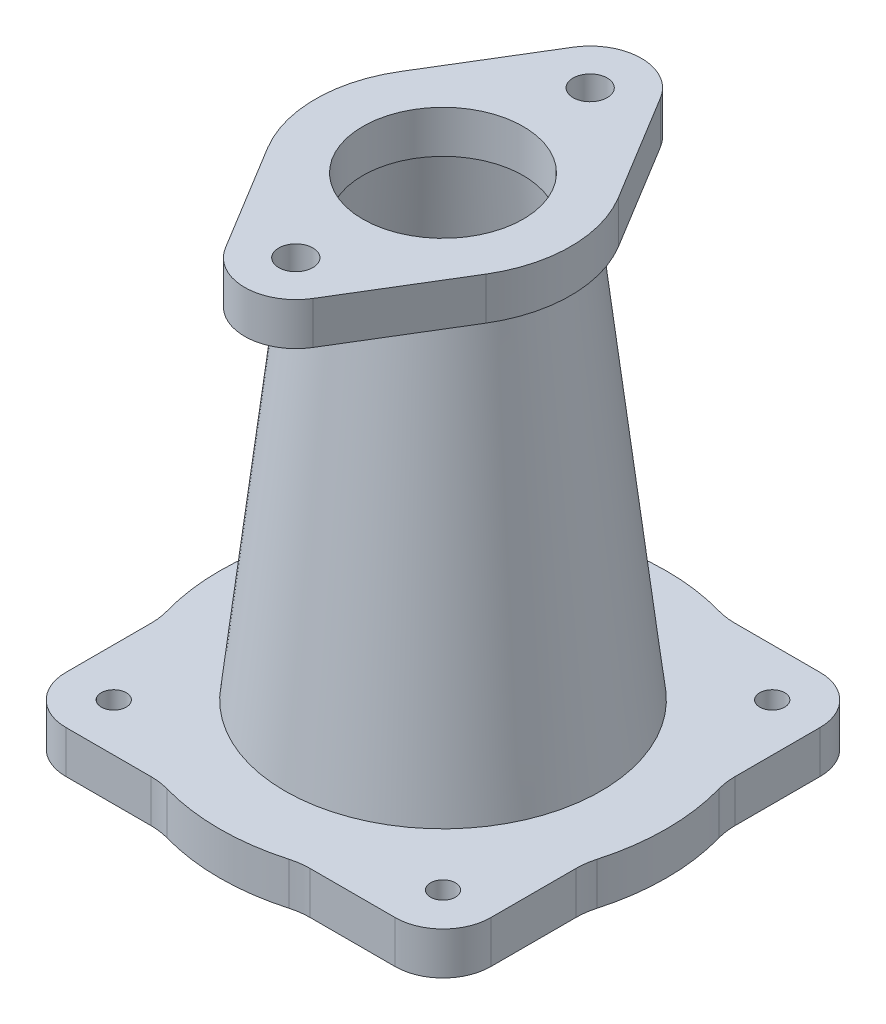
SolidWorks part; units mm, degrees
ref_plane "Front Plane" through (0, 0, 0) normal (0, 0, 1) x (1, 0, 0)
ref_plane "Top Plane" through (0, 0, 0) normal (0, 1, 0) x (1, 0, 0)
ref_plane "Right Plane" through (0, 0, 0) normal (1, 0, 0) x (0, 0, -1)
sketch "Sketch1" plane through (0, 0, 0) normal (1, 0, 0) x (0, 0, -1)
  line L0 (0, 0) -> (0, 51.6773) construction
  line L1 (12, 74.5842) -> (15.8346, 74.5842)
  line L2 (15.8346, 74.5842) -> (24.3324, 0)
  line L3 (24.3324, 0) -> (20.4978, 0)
  line L4 (20.4978, 0) -> (12, 74.5842)
  line L5 (6.7611, 0) -> (-6.7611, 0) construction
  dimension "D1" = 3.81
  dimension "D2" = 83.5
  dimension "D3" = 20.4978
  dimension "D4" = 12
revolve "Revolve1" add sketch "Sketch1" angle 360 about L0
sketch "Sketch2" plane through (0, 0, 0) normal (0, -1, 0) x (1, 0, 0)
  line L1 (0, 0) -> (0, 15.1186) construction
  line L2 (0, 0) -> (14.8797, 0) construction
  line L3 (-31.75, 11.8791) -> (-31.75, 24.6063)
  line L4 (-24.6062, -31.75) -> (-11.8791, -31.75)
  line L5 (-31.75, -24.6062) -> (-31.75, -11.8791)
  line L6 (-24.6062, 31.75) -> (-11.8791, 31.75)
  line L7 (31.75, -24.6062) -> (31.75, -11.8791)
  line L8 (11.8791, 31.75) -> (24.6063, 31.75)
  line L9 (31.75, 11.8791) -> (31.75, 24.6063)
  line L10 (11.8791, -31.75) -> (24.6063, -31.75)
  circle A4 centre (0, 0) radius 22.1742
  circle A5 centre (24.6063, 24.6063) radius 1.8669
  circle A6 centre (24.6063, -24.6062) radius 1.8669
  circle A7 centre (-24.6062, -24.6062) radius 1.8669
  circle A8 centre (-24.6062, 24.6063) radius 1.8669
  arc A9 (-24.6062, 31.75) -> (-31.75, 24.6063) centre (-24.6062, 24.6063) ccw
  arc A10 (24.6063, -31.75) -> (31.75, -24.6062) centre (24.6063, -24.6062) ccw
  arc A11 (-31.75, -24.6062) -> (-24.6062, -31.75) centre (-24.6062, -24.6062) ccw
  arc A12 (31.75, 24.6063) -> (24.6063, 31.75) centre (24.6063, 24.6063) ccw
  arc A13 (-32.1351, 9.1085) -> (-32.1351, -9.1085) centre (0, 0) ccw
  arc A14 (-9.1085, -32.1351) -> (9.1085, -32.1351) centre (0, 0) ccw
  arc A15 (9.1085, 32.1351) -> (-9.1085, 32.1351) centre (0, 0) ccw
  arc A16 (32.1351, -9.1085) -> (32.1351, 9.1085) centre (0, 0) ccw
  arc A17 (32.1351, 9.1085) -> (31.75, 11.8791) centre (41.91, 11.8791) cw
  arc A18 (31.75, -11.8791) -> (32.1351, -9.1085) centre (41.91, -11.8791) cw
  arc A19 (9.1085, -32.1351) -> (11.8791, -31.75) centre (11.8791, -41.91) cw
  arc A20 (-9.1085, -32.1351) -> (-11.8791, -31.75) centre (-11.8791, -41.91) ccw
  arc A21 (-31.75, -11.8791) -> (-32.1351, -9.1085) centre (-41.91, -11.8791) ccw
  arc A22 (-32.1351, 9.1085) -> (-31.75, 11.8791) centre (-41.91, 11.8791) ccw
  arc A23 (-9.1085, 32.1351) -> (-11.8791, 31.75) centre (-11.8791, 41.91) cw
  arc A24 (11.8791, 31.75) -> (9.1085, 32.1351) centre (11.8791, 41.91) cw
  point P0 (0, 0)
  point P12 (0, 0)
  point P13 (0, 0)
  dimension "D3" = 3.7338
  dimension "D4" = 44.3484
  dimension "D19" = 10.16
  dimension "D5" = 31.75
  dimension "D6" = 31.75
  dimension "D11" = 7.1437
  dimension "D12" = 7.1437
  dimension "D13" = 7.1437
  dimension "D14" = 7.1437
  dimension "D15" = 7.1437
  dimension "D16" = 7.1437
  dimension "D17" = 7.1437
  dimension "D18" = 7.1437
  dimension "D20" = 49.2125
extrude "Boss-Extrude1" add sketch "Sketch2" against normal blind 6.35
sketch "Sketch3" plane through (0, 74.5842, 0) normal (0, 1, 0) x (1, 0, 0)
  line L0 (0, 0) -> (21.5903, 0) construction
  line L2 (6.5434, -25.9787) -> (16.3097, -9.9171)
  line L3 (-16.3097, -9.9171) -> (-6.5434, -25.9787)
  line L4 (-16.3097, 9.9171) -> (-6.5434, 25.9787)
  line L5 (6.5434, 25.9787) -> (16.3097, 9.9171)
  circle A0 centre (0, 0) radius 12 construction
  circle A1 centre (0, 0) radius 12
  circle A2 centre (0, 22) radius 2.5527
  circle A3 centre (0, -22) radius 2.5527
  arc A4 (6.5434, 25.9787) -> (-6.5434, 25.9787) centre (0, 22) ccw
  arc A5 (-6.5434, -25.9787) -> (6.5434, -25.9787) centre (0, -22) ccw
  arc A6 (16.3097, -9.9171) -> (16.3097, 9.9171) centre (0, 0) ccw
  arc A7 (-16.3097, 9.9171) -> (-16.3097, -9.9171) centre (0, 0) ccw
  point P20 (4.9545, -23.2322)
  dimension "D1" = 44
  dimension "D2" = 5.1054
  dimension "D3" = 38.1762
  dimension "D4" = 15.3162
extrude "Boss-Extrude2" add sketch "Sketch3" against normal blind 6.35
